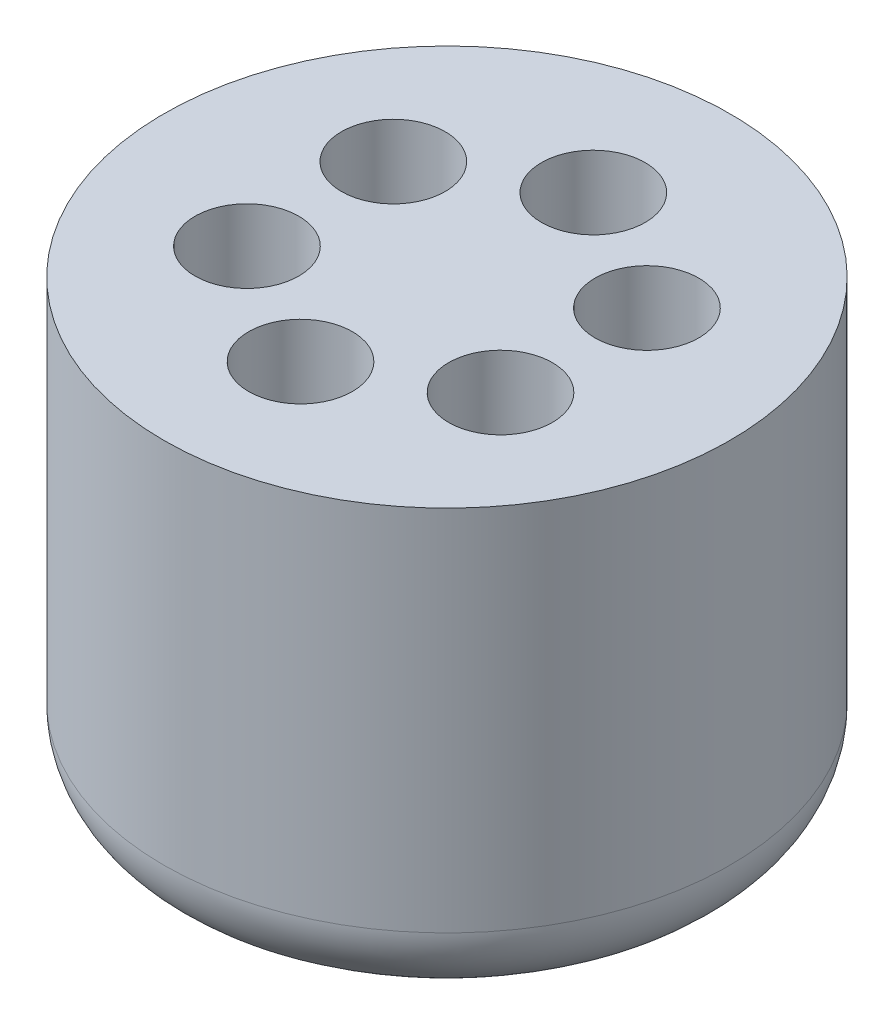
SolidWorks part; units mm, degrees
ref_plane "Front Plane" through (0, 0, 0) normal (0, 0, 1) x (1, 0, 0)
ref_plane "Top Plane" through (0, 0, 0) normal (0, 1, 0) x (1, 0, 0)
ref_plane "Right Plane" through (0, 0, 0) normal (1, 0, 0) x (0, 0, -1)
sketch "Sketch1" plane through (0, 0, 0) normal (0, 1, 0) x (1, 0, 0)
  circle A0 centre (0, 0) radius 30
extrude "Boss-Extrude1" add sketch "Sketch1" along normal blind 47
sketch "Sketch2" plane through (0, 47, 0) normal (0, 1, 0) x (1, 0, 0)
  circle A0 centre (0, 15.52) radius 5.5
  circle A2 centre (-13.4407, 7.76) radius 5.5
  circle A3 centre (-13.4407, -7.76) radius 5.5
  circle A4 centre (0, -15.52) radius 5.5
  circle A5 centre (13.4407, -7.76) radius 5.5
  circle A6 centre (13.4407, 7.76) radius 5.5
  dimension "D1" = 15.52
extrude "Cut-Extrude1" cut sketch "Sketch2" against normal blind 32
fillet "Fillet1" radius 8 1 edges at (0, 0, 30)
extrude "Cut-Extrude2" cut sketch "Sketch2<3>" against normal blind 35
sketch "Sketch2<3>" plane through (0, 47, 0) normal (0, 1, 0) x (1, 0, 0) same geometry as "Sketch2"
